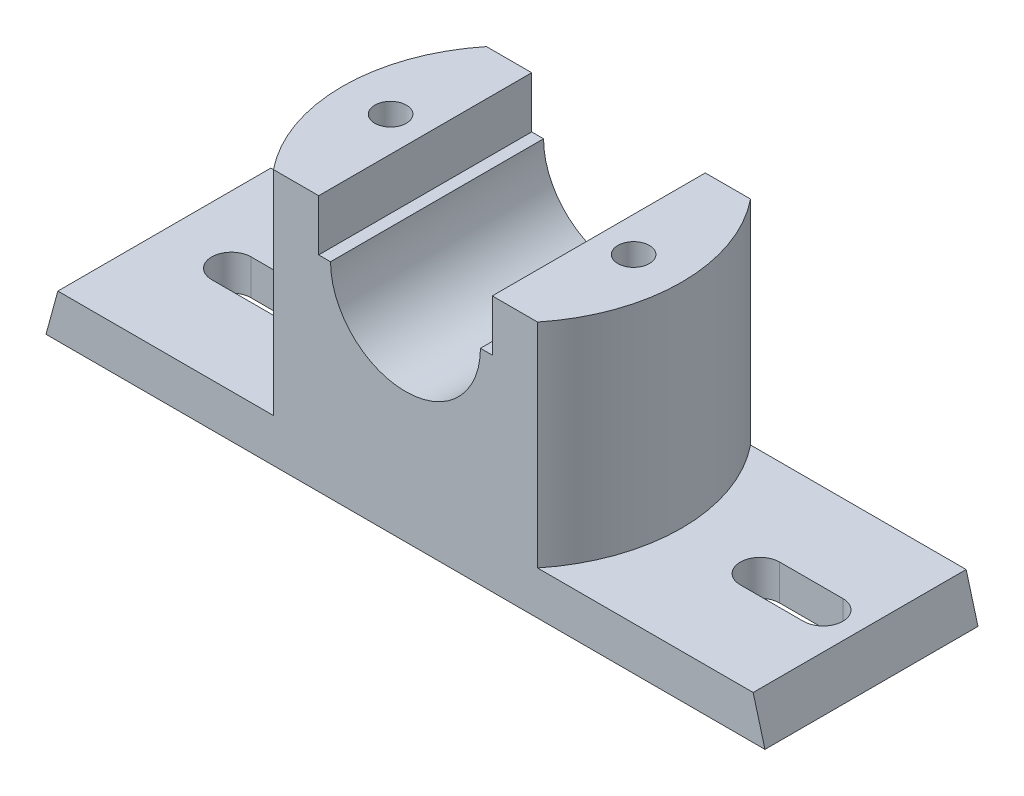
SolidWorks part; units mm, degrees
ref_plane "Front Plane" through (0, 0, 0) normal (0, 0, 1) x (1, 0, 0)
ref_plane "Top Plane" through (0, 0, 0) normal (0, 1, 0) x (1, 0, 0)
ref_plane "Right Plane" through (0, 0, 0) normal (1, 0, 0) x (0, 0, -1)
sketch "Sketch1" plane through (0, 0, 0) normal (0, 0, 1) x (1, 0, 0)
  line L1 (-95, 0) -> (87.2641, 0)
  line L2 (-95, 0) -> (-92, 11)
  line L3 (-92, 11) -> (84.2641, 11)
  line L4 (84.2641, 11) -> (87.2641, 0)
extrude "Boss-Extrude1" add sketch "Sketch1" along normal blind 54
sketch "Sketch2" plane through (0, 11, 0) normal (0, 1, 0) x (1, 0, 0)
  line L0 (84.2641, -54) -> (-92, -54) construction
  line L1 (84.2641, -54) -> (84.2641, 0)
  line L2 (84.2641, 0) -> (-92, 0) construction
  circle A0 centre (-3.8679, -27) radius 43
  point P4 (-3.8679, -27)
  line M1 (84.2641, 0) -> (-92, 0)
  line M3 (-92, -54) -> (84.2641, -54)
extrude "Boss-Extrude2" add sketch "Sketch2" along normal blind 54 contours A0 M3 M1 region at (-3.8679, 11, 27)
sketch "Sketch3" plane through (0, 0, 0) normal (0, 0, 1) x (1, 0, 0)
  line L0 (15.1321, 52) -> (18.1321, 52)
  line L1 (-37.3343, 65) -> (29.5985, 65) construction
  line L2 (-25.8679, 65) -> (-25.8679, 52)
  line L3 (-25.8679, 52) -> (-22.8679, 52)
  line L4 (18.1321, 65) -> (-25.8679, 65)
  line L7 (18.1321, 65) -> (18.1321, 52)
  arc A0 (-22.8679, 52) -> (15.1321, 52) centre (-3.8679, 52) ccw
extrude "Cut-Extrude4" cut sketch "Sketch3" against normal mid plane 159.9174
sketch "Sketch4" plane through (0, 0, 0) normal (0, 1, 0) x (1, 0, 0)
  circle A0 centre (-34.6465, -27) radius 4
extrude "Cut-Extrude8" cut sketch "Sketch4" along normal blind 120 and the other way blind 57
sketch "Sketch5" plane through (0, 0, 0) normal (0, 1, 0) x (1, 0, 0)
  circle A0 centre (26.963, -27) radius 4
extrude "Cut-Extrude10" cut sketch "Sketch5" along normal blind 155 and the other way blind 93
sketch "Sketch6" plane through (0, 11, 0) normal (0, 1, 0) x (1, 0, 0)
  line L0 (75, -27) -> (59, -27) construction
  line L1 (75, -32) -> (59, -32)
  line L2 (75, -22) -> (59, -22)
  line L3 (-59, -27) -> (-75, -27) construction
  line L4 (-59, -32) -> (-75, -32)
  line L5 (-59, -22) -> (-75, -22)
  arc A0 (75, -32) -> (75, -22) centre (75, -27) ccw
  arc A1 (59, -22) -> (59, -32) centre (59, -27) ccw
  arc A2 (-59, -32) -> (-59, -22) centre (-59, -27) ccw
  arc A3 (-75, -22) -> (-75, -32) centre (-75, -27) ccw
  point P2 (67, -27)
  point P9 (-67, -27)
extrude "Cut-Extrude11" cut sketch "Sketch6" against normal blind 155
sketch "Sketch7" plane through (0, 0, 0) normal (0, -1, 0) x (1, 0, 0)
  line L1 (-83.7257, 43.2305) -> (-21.1474, 43.2305)
  line L2 (-83.7257, 43.2305) -> (-83.7257, 8.7488)
  line L3 (-83.7257, 8.7488) -> (-21.1474, 8.7488)
  line L4 (-21.1474, 43.2305) -> (-21.1474, 8.7488)
  line L5 (9.9493, 10.335) -> (83.9734, 10.335)
  line L6 (9.9493, 10.335) -> (9.9493, 43.2305)
  line L7 (9.9493, 43.2305) -> (83.9734, 43.2305)
  line L8 (83.9734, 10.335) -> (83.9734, 43.2305)
extrude "Cut-Extrude12" cut sketch "Sketch7" against normal blind 2
sketch "Sketch8" plane through (0, 0, 0) normal (0, -1, 0) x (1, 0, 0)
  line L0 (-38.7288, 18.9245) -> (-28.2819, 18.9245)
  line L1 (22.8526, 18.843) -> (33.4507, 18.843)
  line L2 (22.8526, 18.843) -> (22.8526, 30.2749)
  line L3 (22.8526, 30.2749) -> (33.4507, 30.2749)
  line L4 (33.4507, 18.843) -> (33.4507, 30.2749)
  line L5 (22.8526, 18.843) -> (33.4507, 30.2749) construction
  line L6 (22.8526, 30.2749) -> (33.4507, 18.843) construction
  line L7 (-38.7288, 18.9245) -> (-38.7288, 30.1934)
  line L8 (-38.7288, 30.1934) -> (-28.2819, 30.1934)
  line L9 (-28.2819, 18.9245) -> (-28.2819, 30.1934)
  line L10 (-38.7288, 18.9245) -> (-28.2819, 30.1934) construction
  line L11 (-38.7288, 30.1934) -> (-28.2819, 18.9245) construction
  point P0 (28.1517, 24.559)
  point P6 (-33.5053, 24.559)
